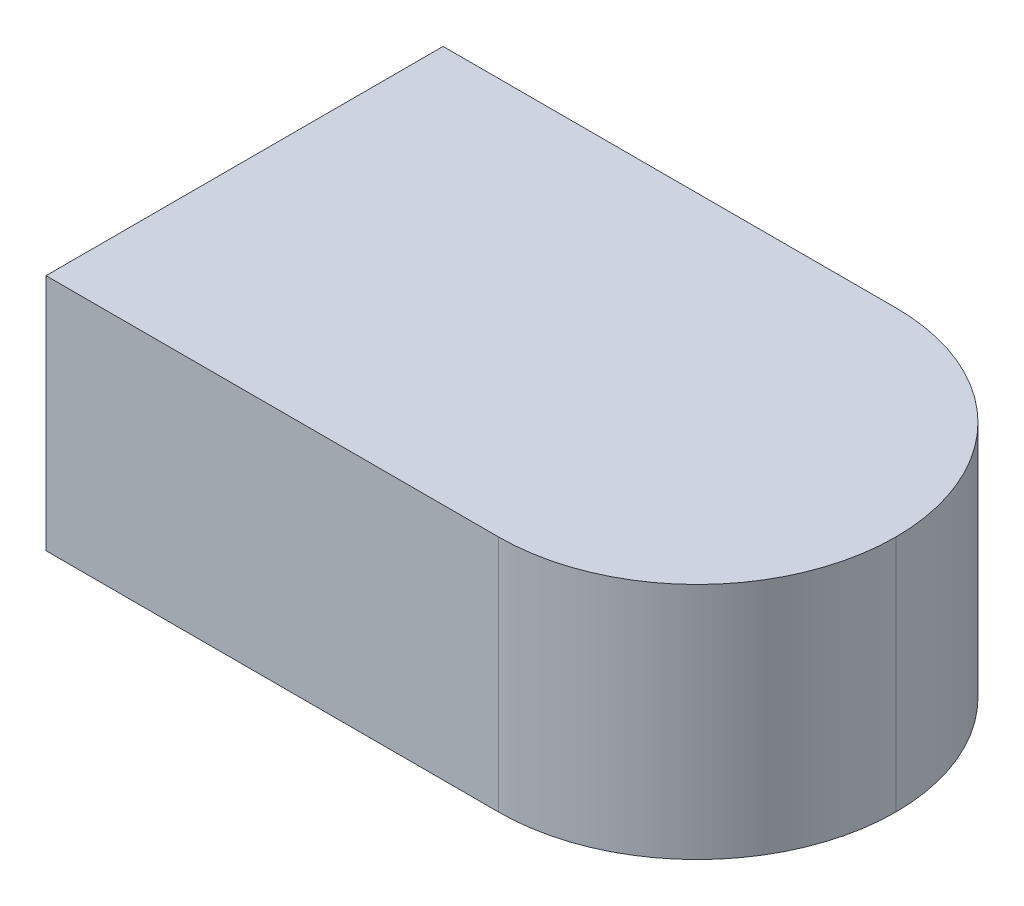
SolidWorks part; units mm, degrees
ref_plane "Front Plane" through (0, 0, 0) normal (0, 0, 1) x (1, 0, 0)
ref_plane "Top Plane" through (0, 0, 0) normal (0, 1, 0) x (1, 0, 0)
ref_plane "Right Plane" through (0, 0, 0) normal (1, 0, 0) x (0, 0, -1)
sketch "Sketch1" plane through (0, 0, 0) normal (0, 1, 0) x (1, 0, 0)
  line L1 (-0.205, -0.125) -> (0.205, -0.125)
  line L2 (-0.205, -0.125) -> (-0.205, 0.125)
  line L3 (-0.205, 0.125) -> (0.205, 0.125)
  line L4 (0.205, -0.125) -> (0.205, 0.125)
  line L5 (-0.205, -0.125) -> (0.205, 0.125) construction
  line L6 (-0.205, 0.125) -> (0.205, -0.125) construction
  point P0 (0, 0)
  dimension "D1" = 0.25
  dimension "D2" = 0.41
extrude "Boss-Extrude1" add sketch "Sketch1" along normal blind 0.15
fillet "Fillet1" radius 0.125 2 edges at (0.205, 0.075, -0.125) (0.205, 0.075, 0.125)
